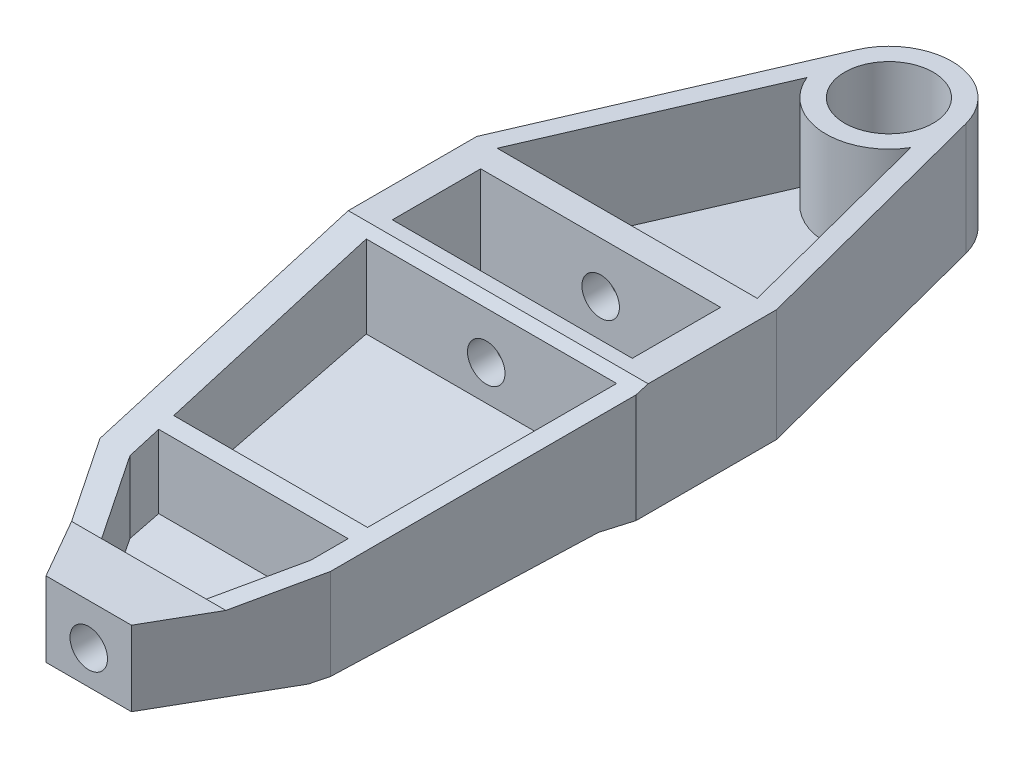
SolidWorks part; units mm, degrees
ref_plane "Ground Plane" through (0, 0, 0) normal (0, 0, 1) x (1, 0, 0)
ref_plane "Side Plane" through (0, 0, 0) normal (0, 1, 0) x (1, 0, 0)
ref_plane "Rear Axle Centerline" through (0, 0, 0) normal (1, 0, 0) x (0, 0, -1)
sketch "Chassis Side View" plane through (0, 0, 0) normal (0, 1, 0) x (1, 0, 0)
  line L0 (0, -381) -> (2300, -381) construction
  line L1 (1150, -381) -> (1150, -856.742)
  line L2 (2150, -381) -> (2150, -1062.9307) construction
  line L3 (-753.0356, 0) -> (753.0356, 0) construction
  line L4 (2450, -381) -> (2450, -1062.9307) construction
  dimension "D1" = 2300
  dimension "D2" = 475.742
  dimension "D3" = 1150
  dimension "D4" = 381
  dimension "D5" = 150
  dimension "D6" = 150
ref_plane "Front Axle Centerline" through (2300, 0, 0) normal (1, 0, 0) x (0, 0, -1)
sketch "Front Wheel Assy Constraints" plane through (2300, 0, 0) normal (1, 0, 0) x (0, 0, -1)
  line L0 (0, 727.5) -> (0, 822.5)
  line L1 (0, 822.5) -> (-271.78, 822.5)
  line L2 (-271.78, 822.5) -> (-551.18, 822.5)
  line L3 (-551.18, 822.5) -> (-551.18, 727.5)
  line L4 (-551.18, 775) -> (0, 775) construction
  line L5 (-271.78, 822.5) -> (-271.78, 775) construction
  line L6 (-551.18, 727.5) -> (-445.4516, 727.5)
  line L7 (-445.4516, 727.5) -> (-445.4516, 798.5)
  line L8 (-445.4516, 798.5) -> (-105.7284, 798.5)
  line L9 (-105.7284, 798.5) -> (-105.7284, 727.5)
  line L10 (-105.7284, 727.5) -> (0, 727.5)
  line L11 (0, 0) -> (-673.9047, 0) construction
  line L13 (0, 753.0356) -> (0, -753.0356) construction
  dimension "D1" = 95
  dimension "D2" = 279.4
  dimension "D3" = 271.78
  dimension "D4" = 23.5
  dimension "D5" = 1550
sketch "Front Sus Front View" plane through (2300, 0, 0) normal (1, 0, 0) x (0, 0, -1)
  line L0 (0, 775) -> (0, 768.65) construction
  line L1 (0, 753.0356) -> (0, -753.0356) construction
  line L2 (0, 768.65) -> (-762, 634.2888) construction
  line L3 (0, 768.65) -> (-745.3671, 768.65) construction
  line L4 (-366.7919, -1090.2477) -> (-525.9451, 520.8571) construction
  line L5 (-366.7919, -1090.2477) -> (-379.5678, 520.8571) construction
  line L6 (-366.7919, -1090.2477) -> (0, 775) construction
  line L7 (-525.9451, 520.8571) -> (-541, 673.2571)
  line L8 (-379.5678, 520.8571) -> (-381, 701.4694)
  line L9 (0, 0) -> (-152.4, 0) construction
  line L13 (-525.9451, 520.8571) -> (-379.5678, 520.8571) construction
  dimension "D1" = 6.35
  dimension "D2" = 10
  dimension "D3" = 152.4
  dimension "D4" = 1865.2477
  dimension "D7" = 541
  dimension "D8" = 153.1418
ref_plane "Fron Wheel Side View Plane" through (0, 775, 0) normal (0, 1, 0) x (1, 0, 0)
sketch "Front SVSA" plane through (0, 775, 0) normal (0, 1, 0) x (1, 0, 0)
  line L0 (2271.684, -676.7175) -> (2328.316, 133.1575)
  line L1 (2300, 0) -> (2300, -771.0839) construction
  line L2 (2300, 0) -> (-2450.054, -116.0888) construction
  line L3 (-2450.054, -116.0888) -> (2298.2335, -297.0415) construction
  line L4 (-753.0356, 0) -> (753.0356, 0) construction
  point P5 (2300, -271.78)
  dimension "D1" = 4
  dimension "D2" = 1.4
  dimension "D3" = 4750.054
sketch3d "Front Chassis Side Axes"
  line L0 (2300, 520.8571, 379.5678) -> (2300, 701.4694, 381) construction
  line L1 (2300, 520.8571, 525.9451) -> (2300, 673.2571, 541) construction
  line L2 (2300, 520.8571, 379.5678) -> (2300, 701.4694, 381) construction
  line L3 (2300, 520.8571, 525.9451) -> (2300, 673.2571, 541) construction
  line L4 (2300, 673.2571, 541) -> (2300, 775, 551.0507) construction
  line L5 (2300, 701.4694, 381) -> (2300, 775, 381.5831) construction
  line L6 (2300, 775, 0) -> (2300, 775, 771.0839) construction
  line L7 (-2450.054, 775, 116.0888) -> (2349.7917, 775, 555.6101) construction
  line L8 (-2450.054, 775, 116.0888) -> (2349.9221, 775, 384.3734) construction
  line L9 (2349.9221, 775, 384.3734) -> (2177.377, 520.8571, 372.714) construction
  line L10 (2349.7917, 775, 555.6101) -> (2225.4174, 520.8571, 519.1156) construction
  line L11 (2300, 520.8571, 525.9451) -> (2300, 520.8571, 519.1156) construction
  line L12 (2300, 520.8571, 519.1156) -> (2225.4174, 520.8571, 519.1156) construction
  line L13 (2598.7501, 520.8571, 553.3017) -> (1702.4998, 520.8571, 471.2321)
  line L14 (2300, 520.8571, 379.5678) -> (2300, 520.8571, 372.714) construction
  line L15 (2300, 520.8571, 372.714) -> (2177.377, 520.8571, 372.714) construction
  line L16 (2599.5325, 520.8571, 396.3095) -> (1700.935, 520.8571, 346.0843)
  dimension "D1" = 50
  dimension "D2" = 50
  dimension "D3" = 600
  dimension "D4" = 300
  dimension "D5" = 600
  dimension "D6" = 300
sketch3d "Front Left Control Arm"
  line L0 (2300, 520.8571, 379.5678) -> (2300, 701.4694, 381) construction
  line L2 (2300, 520.8571, 379.5678) -> (2300, 701.4694, 381) construction
  line L3 (2300, 520.8571, 525.9451) -> (2300, 673.2571, 541) construction
  line L4 (2598.7501, 520.8571, 553.3017) -> (1702.4998, 520.8571, 471.2321) construction
  line L5 (2599.5325, 520.8571, 396.3095) -> (1700.935, 520.8571, 346.0843) construction
  line L6 (2598.7501, 520.8571, 553.3017) -> (1702.4998, 520.8571, 471.2321) construction
  line L7 (2599.5325, 520.8571, 396.3095) -> (1700.935, 520.8571, 346.0843) construction
  line L8 (2450, 520.8571, 539.6806) -> (2280.5957, 673.2571, 539.2232)
  line L9 (2280.5957, 673.2571, 539.2232) -> (2150, 520.8571, 512.2097)
  line L10 (2300, 520.8571, 525.9451) -> (2300, 673.2571, 541) construction
  line L11 (2300, 673.2571, 541) -> (2280.5957, 673.2571, 539.2232) construction
  line L12 (2271.684, 775, 676.7175) -> (2328.316, 775, -133.1575) construction
  line L13 (2150, 0, 512.2097) -> (2150, 520.8571, 512.2097) construction
  line L14 (2292.3517, 701.4694, 380.5725) -> (2292.3517, 775, 381.1556) construction
  line L15 (2150, 0, 381) -> (2150, 0, 1062.9307) construction
  line L16 (2450, 0, 539.6806) -> (2450, 520.8571, 539.6806) construction
  line L17 (2450, 0, 381) -> (2450, 0, 1062.9307) construction
  line L18 (2450, 520.8571, 387.9517) -> (2292.3517, 701.4694, 380.5725)
  line L19 (2292.3517, 701.4694, 380.5725) -> (2150, 520.8571, 371.1838)
  line L20 (2300, 701.4694, 381) -> (2292.3517, 701.4694, 380.5725) construction
  line L21 (2450, 0, 387.9517) -> (2450, 520.8571, 387.9517) construction
  line L22 (2150, 0, 371.1838) -> (2150, 520.8571, 371.1838) construction
  line L23 (2280.5957, 673.2571, 539.2232) -> (2280.5957, 775, 549.2738) construction
sketch3d "Front Control Arm"
  line L0 (2450, 520.8571, 387.9517) -> (2292.3517, 701.4694, 380.5725) construction
  line L1 (2292.3517, 701.4694, 380.5725) -> (2150, 520.8571, 371.1838) construction
  line L2 (2280.5957, 673.2571, 539.2232) -> (2150, 520.8571, 512.2097) construction
  line L3 (2450, 520.8571, 539.6806) -> (2280.5957, 673.2571, 539.2232) construction
  line L4 (2450, 520.8571, 387.9517) -> (2292.3517, 701.4694, 380.5725)
  line L5 (2292.3517, 701.4694, 380.5725) -> (2150, 520.8571, 371.1838)
  line L6 (2280.5957, 673.2571, 539.2232) -> (2150, 520.8571, 512.2097)
  line L7 (2450, 520.8571, 539.6806) -> (2280.5957, 673.2571, 539.2232)
  line L8 (2450, -520.8571, 539.6806) -> (2280.5957, -673.2571, 539.2232)
  line L9 (2280.5957, -673.2571, 539.2232) -> (2150, -520.8571, 512.2097)
  line L10 (2292.3517, -701.4694, 380.5725) -> (2150, -520.8571, 371.1838)
  line L11 (2450, -520.8571, 387.9517) -> (2292.3517, -701.4694, 380.5725)
ref_plane "Max Droop Plane" through (0, 0, -25.4) normal (0, 0, 1) x (1, 0, 0)
sketch3d "Shock"
  line L0 (2292.3517, 701.4694, 380.5725) -> (2293.5626, 664.4705, 414.2387) construction
  line L1 (2300, 520.8571, 525.9451) -> (2298.2629, 520.8571, 544.9158) construction
  line L2 (2150, 520.8571, 512.2097) -> (2450, 520.8571, 539.6806) construction
  line L3 (2300, 520.8571, 525.9451) -> (2300, 230.5152, 525.9451) construction
  line L4 (2293.5626, 664.4705, 414.2387) -> (2298.2629, 520.8571, 544.9158)
  dimension "D1" = 50.038
  dimension "D2" = 19.05
sketch3d "Parametric Analysis"
  line L2 (2300, 822.5, 0) -> (2300, 822.5, 271.78) construction
  line L3 (2300.4137, 822.5, 271.7939) -> (2300.4137, 822.5, -88.8537) construction
  line L4 (2450, 520.8571, 387.9517) -> (2292.3526, 701.4695, 380.5568)
  line L5 (2292.3526, 701.4695, 380.5568) -> (2150, 520.8571, 371.1838)
  line L6 (2450, 520.8571, 539.6806) -> (2280.5972, 673.2586, 539.2077)
  line L7 (2280.5972, 673.2586, 539.2077) -> (2150, 520.8571, 512.2097)
  line L8 (2292.3517, 701.4694, 380.5725) -> (2300, 822.5, 271.78) construction
  line L9 (2450, 520.8571, 387.9517) -> (2292.3517, 701.4694, 380.5725) construction
  line L10 (2292.3517, 701.4694, 380.5725) -> (2150, 520.8571, 371.1838) construction
  line L11 (2450, 520.8571, 539.6806) -> (2280.5957, 673.2571, 539.2232) construction
  line L12 (2280.5957, 673.2571, 539.2232) -> (2150, 520.8571, 512.2097) construction
  line L13 (2280.5957, 673.2571, 539.2232) -> (2292.3517, 701.4694, 380.5725) construction
  line L14 (2300, 822.5, 271.78) -> (2280.5957, 673.2571, 539.2232) construction
  line L15 (2300, 822.5, 271.78) -> (2300.4132, 720.8156, 271.78) construction
  line L16 (2280.5972, 673.2586, 539.2077) -> (2300.4137, 822.5, 271.7939) construction
  line L17 (2300.4137, 822.5, 271.7939) -> (2292.3526, 701.4695, 380.5568) construction
  line L18 (2280.5972, 673.2586, 539.2077) -> (2292.3526, 701.4695, 380.5568) construction
  line L19 (2300.4137, 822.5, 271.7939) -> (2300.4137, 720.8148, 271.7641) construction
  line L23 (2292.3517, 701.4694, 380.5725) -> (2265.8007, 667.7821, 378.8214) construction
  line L30 (2265.8007, 667.7821, 378.8214) -> (2325.2406, 663.7898, 382.112) construction
  line L31 (2325.2406, 663.7898, 382.112) -> (2293.5626, 664.4705, 414.2387) construction
  line L32 (2292.3517, 701.4694, 380.5725) -> (2325.2406, 663.7898, 382.112) construction
  line L33 (2293.5626, 664.4705, 414.2387) -> (2265.8007, 667.7821, 378.8214) construction
  line L34 (2292.3526, 701.4695, 380.5568) -> (2293.5633, 664.4722, 414.2247) construction
  line L35 (2292.3517, 701.4694, 380.5725) -> (2293.5626, 664.4705, 414.2387) construction
  line L39 (2300.4137, 822.5, 271.7939) -> (2300.4137, 822.5798, 0.014)
  line L40 (2300.4137, 822.5798, 0.014) -> (2300.4137, 727.5798, -0.014)
  line L41 (2300, 727.5, 0) -> (2300, 822.5, 0) construction
  line L42 (2298.2629, 520.8571, 544.9158) -> (2293.5633, 664.4722, 414.2247)
  point P5 (2300.4137, 775.0798, 0)
  dimension "D1" = 25.4
  dimension "D2" = 194.2357
  dimension "D3" = 0.0798
  dimension "D4" = 0.017
sketch3d "3DSketch1"
  line L0 (2293.5626, 664.4705, 414.2387) -> (2298.2629, 520.8571, 544.9158) construction
  line L1 (2280.5972, 673.2586, 539.2077) -> (2150, 520.8571, 512.2097) construction
  line L2 (2450, 520.8571, 539.6806) -> (2280.5972, 673.2586, 539.2077) construction
  line L3 (2292.3526, 701.4695, 380.5568) -> (2150, 520.8571, 371.1838) construction
  line L4 (2450, 520.8571, 387.9517) -> (2292.3526, 701.4695, 380.5568) construction
  line L5 (2293.5626, 664.4705, 414.2387) -> (2298.2629, 520.8571, 544.9158)
  line L6 (2280.5972, 673.2586, 539.2077) -> (2150, 520.8571, 512.2097)
  line L7 (2450, 520.8571, 539.6806) -> (2280.5972, 673.2586, 539.2077)
  line L8 (2292.3526, 701.4695, 380.5568) -> (2150, 520.8571, 371.1838)
  line L9 (2450, 520.8571, 387.9517) -> (2292.3526, 701.4695, 380.5568)
  line L10 (2450, 520.8571, 539.6806) -> (2450, 470.0571, 539.6806) construction
  line L11 (2150, 520.8571, 512.2097) -> (2150, 470.0571, 512.2097) construction
  line L12 (2298.2629, 520.8571, 544.9158) -> (2298.2629, 470.0571, 544.9158) construction
  line L13 (2450, 520.8571, 387.9517) -> (2450, 470.0571, 387.9517) construction
  line L14 (2150, 520.8571, 371.1838) -> (2150, 470.0571, 371.1838) construction
  line L15 (2150, -520.8571, 512.2097) -> (2150, -470.0571, 512.2097) construction
  line L16 (2298.2629, -520.8571, 544.9158) -> (2298.2629, -470.0571, 544.9158) construction
  line L17 (2450, -520.8571, 539.6806) -> (2450, -470.0571, 539.6806) construction
  line L18 (2293.5626, -664.4705, 414.2387) -> (2298.2629, -520.8571, 544.9158)
  line L19 (2280.5972, -673.2586, 539.2077) -> (2150, -520.8571, 512.2097)
  line L20 (2450, -520.8571, 539.6806) -> (2280.5972, -673.2586, 539.2077)
  line L21 (2450, -520.8571, 387.9517) -> (2450, -470.0571, 387.9517) construction
  line L22 (2150, -520.8571, 371.1838) -> (2150, -470.0571, 371.1838) construction
  line L23 (2292.3526, -701.4695, 380.5568) -> (2150, -520.8571, 371.1838)
  line L24 (2450, -520.8571, 387.9517) -> (2292.3526, -701.4695, 380.5568)
  line L27 (2300, 775, 551.18) -> (2300, 775, 0) construction
  dimension "D1" = 50.8
  dimension "D2" = 304.9478
  dimension "D3" = 544.9185
ref_plane "Plane1" through (0, 718.612, 0) normal (0, 1, 0) x (1, 0, 0)
sketch "Sketch1" plane through (0, 718.612, 0) normal (0, 1, 0) x (1, 0, 0)
  line L0 (2300, 0) -> (2300, -551.18) construction
  line L1 (2300, 0) -> (2300, -673.9047) construction
  line L2 (-753.0356, 0) -> (753.0356, 0) construction
  line L3 (2300, -275.59) -> (2280.5957, -539.2232) construction
  line L4 (2295.0737, -527.2852) -> (2266.1177, -527.2852)
  line L5 (2295.0737, -527.2852) -> (2319.6398, -484.4331)
  line L6 (2319.6398, -484.4331) -> (2343.1517, -404.3723)
  line L7 (2343.1517, -404.3723) -> (2343.1517, -356.7727)
  line L8 (2343.1517, -356.7727) -> (2320.6639, -270.2211)
  line L9 (2266.1177, -527.2852) -> (2241.5517, -484.4331)
  line L10 (2241.5517, -484.4331) -> (2241.5517, -356.7727)
  line L11 (2280.4102, -267.1009) -> (2241.5517, -356.7727)
  line L12 (2332.9917, -380.5725) -> (2251.7117, -380.5725) construction
  line L13 (2343.1517, -356.7727) -> (2241.5517, -356.7727) construction
  line L14 (2332.9917, -365.6119) -> (2251.7117, -365.6119)
  line L15 (2332.9917, -365.6119) -> (2332.9917, -395.5331)
  line L16 (2332.9917, -395.5331) -> (2251.7117, -395.5331)
  line L17 (2251.7117, -365.6119) -> (2251.7117, -395.5331)
  line L18 (2332.9917, -365.6119) -> (2251.7117, -395.5331) construction
  line L19 (2332.9917, -395.5331) -> (2251.7117, -365.6119) construction
  line L20 (2343.1517, -404.3723) -> (2241.5517, -404.3723) construction
  line L21 (2319.6398, -484.4331) -> (2241.5517, -484.4331) construction
  line L22 (2280.5957, -539.2232) -> (2280.5957, -527.2852) construction
  circle A0 centre (2300, -275.59) radius 15
  arc A1 (2320.6639, -270.2211) -> (2280.4102, -267.1009) centre (2300, -275.59) ccw
  arc A2 (2280.4102, -267.1009) -> (2320.6639, -270.2211) centre (2300, -275.59) ccw construction
  point P21 (2292.3517, -380.5725)
  point P30 (2292.3517, -380.5725)
  dimension "D1" = 30
  dimension "D2" = 42.7
  dimension "D3" = 81.28
  dimension "D4" = 29.9212
  dimension "D5" = 10.16
  dimension "D6" = 10.16
  dimension "D7" = 8.8392
  dimension "D8" = 8.8392
  dimension "D9" = 11.938
  dimension "D10" = 28.956
  dimension "D11" = 88.9
extrude "Boss-Extrude1" add sketch "Sketch1" against normal blind 88.9
sketch "Sketch3" plane through (2300, 0, 0) normal (1, 0, 0) x (0, 0, -1)
  line L0 (-254.24, 680.512) -> (-414.2783, 680.512)
  line L1 (-254.24, 629.712) -> (-254.24, 718.612) construction
  line L2 (-527.2852, 687.2271) -> (-527.2852, 718.612)
  line L3 (-527.2852, 718.612) -> (-400.3083, 718.612)
  line L4 (482.0237, 718.612) -> (-482.0237, 718.612) construction
  line L5 (-414.2783, 680.512) -> (-489.1852, 661.8271)
  line L6 (-489.1852, 661.8271) -> (-527.2852, 661.8271)
  line L7 (-527.2852, 629.712) -> (-527.2852, 718.612) construction
  line L8 (-400.3083, 718.612) -> (-506.9652, 687.2271)
  line L9 (-506.9652, 687.2271) -> (-527.2852, 687.2271)
  line L10 (-404.3723, 629.712) -> (-404.3723, 718.612) construction
  line L11 (-527.2852, 661.8271) -> (-527.2852, 629.712)
  line L12 (-527.2852, 629.712) -> (-254.24, 629.712)
  line L13 (-270.2211, 629.712) -> (-254.24, 629.712) construction
  line L14 (-254.24, 629.712) -> (-254.24, 680.512)
  dimension "D1" = 4.064
  dimension "D2" = 38.1
  dimension "D3" = 38.1
  dimension "D4" = 20.32
  dimension "D5" = 25.4
  dimension "D6" = 11.43
  dimension "D7" = 13.97
extrude "Cut-Extrude1" cut sketch "Sketch3" against normal through all both and the other way through all
sketch "Sketch4" plane through (0, 718.612, 0) normal (0, 1, 0) x (1, 0, 0)
  line L0 (2336.5335, -404.3723) -> (2313.0216, -484.4331)
  line L1 (2343.1517, -404.3723) -> (2241.5517, -404.3723) construction
  line L2 (2319.6398, -484.4331) -> (2241.5517, -484.4331) construction
  line L3 (2313.0216, -484.4331) -> (2300.1045, -506.9652)
  line L4 (2254.4688, -506.9652) -> (2306.7227, -506.9652) construction
  line L5 (2300.1045, -506.9652) -> (2264.6288, -506.9652)
  line L6 (2264.6288, -506.9652) -> (2251.7117, -484.4331)
  line L7 (2251.7117, -484.4331) -> (2251.7117, -404.3723)
  line L8 (2251.7117, -404.3723) -> (2336.5335, -404.3723)
  line L10 (2319.6398, -484.4331) -> (2343.1517, -404.3723) construction
  line L11 (2295.0737, -527.2852) -> (2319.6398, -484.4331) construction
  line L12 (2241.5517, -484.4331) -> (2241.5517, -356.7727) construction
  line L13 (2266.1177, -527.2852) -> (2241.5517, -484.4331) construction
  line L14 (2315.8824, -474.6918) -> (2251.7117, -474.6918)
  line L15 (2317.3743, -469.6118) -> (2251.7117, -469.6118)
  dimension "D1" = 6.35
  dimension "D2" = 10.16
  dimension "D3" = 5.08
extrude "Cut-Extrude2" cut sketch "Sketch4" against normal offset from surface 6.35 and the other way through all contours L15 L0 L8 L7 | L0 L14 L7 L6 L5 L3 region at (2289.5361, 718.612, 435.6077) region at (2282.6255, 718.612, 489.2475) up to face at (2284.0295, 668.4505, 462.6322)
sketch "Sketch5" plane through (0, 718.612, 0) normal (0, 1, 0) x (1, 0, 0)
  line L0 (2300, 0) -> (2300, -673.9047) construction
  line L1 (2314.518, -271.8179) -> (2336.5909, -356.7727)
  line L2 (2336.5909, -356.7727) -> (2248.4723, -356.7727)
  line L3 (2248.4723, -356.7727) -> (2286.2367, -269.6258)
  line L4 (2280.4102, -267.1009) -> (2241.5517, -356.7727) construction
  line L5 (2343.1517, -356.7727) -> (2320.6639, -270.2211) construction
  line L6 (2332.9917, -365.6119) -> (2251.7117, -365.6119) construction
  circle A0 centre (2300, -275.59) radius 15 construction
  circle A1 centre (2300, -275.59) radius 15 construction
  circle A2 centre (2300, -275.59) radius 15 construction
  circle A3 centre (2300, -275.59) radius 21.35
  dimension "D1" = 8.8392
  dimension "D2" = 30
extrude "Cut-Extrude3" cut sketch "Sketch5" against normal blind 31.75 and the other way through all contours A0 L3 L2 L1 region at (2294.8686, 718.612, 328.3478)
sketch "Sketch6" plane through (0, 0, 527.2852) normal (0, 0, 1) x (1, 0, 0)
  circle A0 centre (2280.5957, 673.2571) radius 6.35
  dimension "D1" = 12.7
extrude "Cut-Extrude4" cut sketch "Sketch6" against normal blind 31.75
sketch "Sketch7" plane through (0, 0, 404.3723) normal (0, 0, 1) x (1, 0, 0)
  circle A0 centre (2292.3517, 701.4694) radius 6.35
  dimension "D1" = 12.7
extrude "Cut-Extrude5" cut sketch "Sketch7" against normal blind 50.8
ref_axis "Axis1" through (2270.4507, 648.9089, 676.1444) along (0.0728, 0.1746, -0.9819)
equation "\"wheelbase\"= 2.3m"
equation "\"track_front_outer\"= 1.55m"
equation "\"cg_h\"= 18.73in"
equation "\"cg_b\"= \"wheelbase\" / 2"
equation "\"chassis_ride_height\"= 15in"
equation "\"hub_offset\"= 23.5mm"
equation "\"tire_radius\"= 11in"
equation "\"tire_radius_loaded\"= 10.7in"
equation "\"tire_width\"= 95mm"
equation "\"static_camber\"= 0deg"
equation "\"caster_static\"= 4deg"
equation "\"control_arm_ratio\"= 0.95"
equation "\"roll_center_height\"= 6in"
equation "\"scrub_radius\"= 0.25in"
equation "\"camber_change_rate\"= 0.5deg'per inch of travel"
equation "\"fvsa_length\"= atn ( 1 / \"camber_change_rate\" )"
equation "\"svsa_length\"= 2.5 * \"wheelbase\""
equation "\"svsa_height\"= 1"
equation "\"anti_squat_rear\"= 0.15"
equation "\"front_brakes\"= .75"
equation "\"anti_dive_front\"= 0.1"
equation "\"D1@Chassis Side View\" = \"wheelbase\""
equation "\"D2@Chassis Side View\" = \"cg_h\""
equation "\"D3@Chassis Side View\" = \"cg_b\""
equation "\"D4@Chassis Side View\" = \"chassis_ride_height\""
equation "\"D1@Front Axle Centerline\"=\"wheelbase\""
equation "\"D1@Front Wheel Assy Constraints\" = \"tire_width\""
equation "\"D2@Front Wheel Assy Constraints\" = \"tire_radius\""
equation "\"D3@Front Wheel Assy Constraints\" = \"tire_radius_loaded\""
equation "\"D4@Front Wheel Assy Constraints\" = \"hub_offset\""
equation "\"D1@Front Sus Front View\" = \"scrub_radius\""
equation "\"static_kingpin\"= 10deg"
equation "\"D2@Front Sus Front View\" = \"static_kingpin\""
equation "\"D3@Front Sus Front View\" = \"roll_center_height\""
equation "\"D6@Front Sus Front View\" = \"chassis_ride_height\""
equation "\"D7@Front Sus Front View\"=\"chassis_ride_height\" + 160mm"
equation "\"D1@Front SVSA\" = \"caster_static\""
equation "\"D4@Front Sus Front View\"=\"fvsa_length\"+10"
equation "\"D5@Front Wheel Assy Constraints\"=\"track_front_outer\""
equation "\"phi_front\"= atn ( \"anti_dive_front\" / \"front_brakes\" * \"cg_h\" / \"wheelbase\" )"
equation "\"anti_lift_rear\"= 0.1"
equation "\"a\"= 0"
